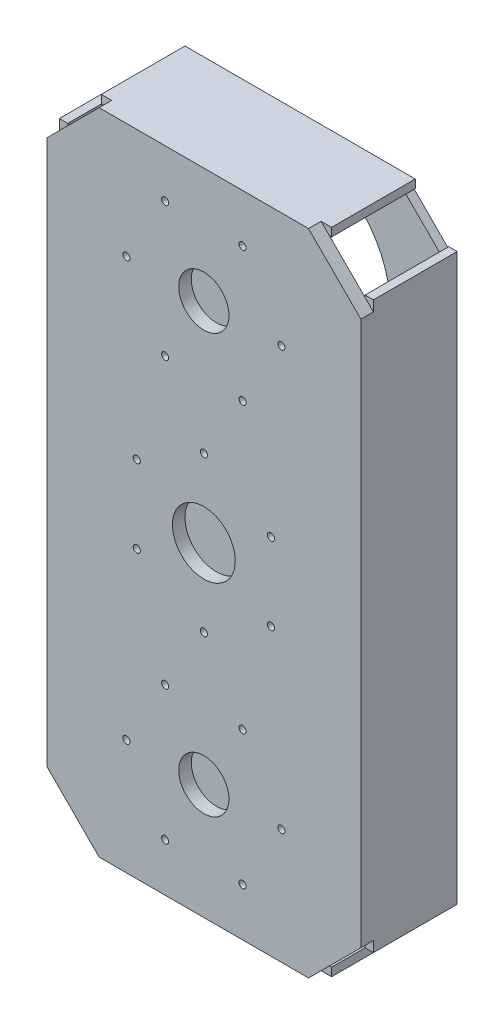
SolidWorks part; units mm, degrees
material "6061-T6 (SS)"
ref_plane "Front Plane" through (0, 0, 0) normal (0, 0, 1) x (1, 0, 0)
ref_plane "Top Plane" through (0, 0, 0) normal (0, 1, 0) x (1, 0, 0)
ref_plane "Right Plane" through (0, 0, 0) normal (1, 0, 0) x (0, 0, -1)
ref_plane "PL_Top_Plate_base" through (0, 0, 131) normal (0, 0, 1) x (1, 0, 0)
sketch "SK_Top_Plate" plane through (0, 0, 131) normal (0, 0, 1) x (1, 0, 0)
  line L0 (-50, -155) -> (50, -155)
  line L1 (50, -155) -> (75, -130)
  line L2 (75, -130) -> (75, 130)
  line L3 (75, 130) -> (50, 155)
  line L4 (50, 155) -> (-50, 155)
  line L5 (-50, 155) -> (-75, 130)
  line L6 (-75, 130) -> (-75, -130)
  line L7 (-75, -130) -> (-50, -155)
  circle A0 centre (37, 100) radius 1.7
  circle A1 centre (18.5, 132.0429) radius 1.7
  circle A2 centre (-18.5, 132.0429) radius 1.7
  circle A3 centre (-37, 100) radius 1.7
  circle A4 centre (-18.5, 67.9571) radius 1.7
  circle A5 centre (18.5, 67.9571) radius 1.7
  circle A6 centre (0, 100) radius 12
  circle A7 centre (37, -100) radius 1.7
  circle A8 centre (18.5, -67.9571) radius 1.7
  circle A9 centre (-18.5, -67.9571) radius 1.7
  circle A10 centre (-37, -100) radius 1.7
  circle A11 centre (-18.5, -132.0429) radius 1.7
  circle A12 centre (18.5, -132.0429) radius 1.7
  circle A13 centre (0, -100) radius 12
  circle A14 centre (32.0429, 18.5) radius 1.7
  circle A15 centre (0, 37) radius 1.7
  circle A16 centre (-32.0429, 18.5) radius 1.7
  circle A17 centre (-32.0429, -18.5) radius 1.7
  circle A18 centre (0, -37) radius 1.7
  circle A19 centre (32.0429, -18.5) radius 1.7
  circle A20 centre (0, 0) radius 15
  dimension "D17_SK_Top_Plate" = 3.4
  dimension "D20_SK_Top_Plate" = 3.4
  dimension "D23_SK_Top_Plate" = 3.4
  dimension "D26_SK_Top_Plate" = 3.4
  dimension "D29_SK_Top_Plate" = 3.4
  dimension "D32_SK_Top_Plate" = 3.4
  dimension "D35_SK_Top_Plate" = 24
  dimension "D37_SK_Top_Plate" = 3.4
  dimension "D40_SK_Top_Plate" = 3.4
  dimension "D43_SK_Top_Plate" = 3.4
  dimension "D46_SK_Top_Plate" = 3.4
  dimension "D49_SK_Top_Plate" = 3.4
  dimension "D52_SK_Top_Plate" = 3.4
  dimension "D55_SK_Top_Plate" = 24
  dimension "D57_SK_Top_Plate" = 3.4
  dimension "D60_SK_Top_Plate" = 3.4
  dimension "D62_SK_Top_Plate" = 3.4
  dimension "D65_SK_Top_Plate" = 3.4
  dimension "D68_SK_Top_Plate" = 3.4
  dimension "D70_SK_Top_Plate" = 3.4
  dimension "D73_SK_Top_Plate" = 30
  dimension "P1" = 50
  dimension "P2" = 155
  dimension "P3" = 50
  dimension "P4" = 155
  dimension "P5" = 75
  dimension "P6" = 130
  dimension "P7" = 75
  dimension "P8" = 130
  dimension "P9" = 50
  dimension "P10" = 155
  dimension "P11" = 50
  dimension "P12" = 155
  dimension "P13" = 75
  dimension "P14" = 130
  dimension "P15" = 75
  dimension "P16" = 130
  dimension "P18" = 37
  dimension "P19" = 100
  dimension "P21" = 18.5
  dimension "P22" = 132.0429
  dimension "P24" = 18.5
  dimension "P25" = 132.0429
  dimension "P27" = 37
  dimension "P28" = 100
  dimension "P30" = 18.5
  dimension "P31" = 67.9571
  dimension "P33" = 18.5
  dimension "P34" = 67.9571
  dimension "P36" = 100
  dimension "P38" = 37
  dimension "P39" = 100
  dimension "P41" = 18.5
  dimension "P42" = 67.9571
  dimension "P44" = 18.5
  dimension "P45" = 67.9571
  dimension "P47" = 37
  dimension "P48" = 100
  dimension "P50" = 18.5
  dimension "P51" = 132.0429
  dimension "P53" = 18.5
  dimension "P54" = 132.0429
  dimension "P56" = 100
  dimension "P58" = 32.0429
  dimension "P59" = 18.5
  dimension "P61" = 37
  dimension "P63" = 32.0429
  dimension "P64" = 18.5
  dimension "P66" = 32.0429
  dimension "P67" = 18.5
  dimension "P69" = 37
  dimension "P71" = 32.0429
  dimension "P72" = 18.5
extrude "Top_Plate" add sketch "SK_Top_Plate" along normal blind 6
ref_plane "PL_Front_Wall_base" through (71, 0, 0) normal (1, 0, 0) x (0, 0, -1)
sketch "SK_Front_Wall" plane through (71, 0, 0) normal (1, 0, 0) x (0, 0, -1)
  line L0 (-91, -135) -> (-91, 135)
  line L1 (-91, 135) -> (-131, 135)
  line L2 (-131, 135) -> (-131, -135)
  line L3 (-131, -135) -> (-91, -135)
  dimension "P1" = 91
  dimension "P2" = 135
  dimension "P3" = 91
  dimension "P4" = 135
  dimension "P5" = 131
  dimension "P6" = 135
  dimension "P7" = 131
  dimension "P8" = 135
extrude "Front_Wall" add sketch "SK_Front_Wall" along normal blind 4
ref_plane "PL_Back_Wall_base" through (-75, 0, 0) normal (1, 0, 0) x (0, 0, -1)
sketch "SK_Back_Wall" plane through (-75, 0, 0) normal (1, 0, 0) x (0, 0, -1)
  line L0 (-91, -135) -> (-91, 135)
  line L1 (-91, 135) -> (-131, 135)
  line L2 (-131, 135) -> (-131, -135)
  line L3 (-131, -135) -> (-91, -135)
  dimension "P1" = 91
  dimension "P2" = 135
  dimension "P3" = 91
  dimension "P4" = 135
  dimension "P5" = 131
  dimension "P6" = 135
  dimension "P7" = 131
  dimension "P8" = 135
extrude "Back_Wall" add sketch "SK_Back_Wall" along normal blind 4
ref_plane "PL_Left_Wall_base" through (0, 151, 0) normal (0, 1, 0) x (1, 0, 0)
sketch "SK_Left_Wall" plane through (0, 151, 0) normal (0, 1, 0) x (1, 0, 0)
  line L0 (-55, -91) -> (55, -91)
  line L1 (55, -91) -> (55, -131)
  line L2 (55, -131) -> (-55, -131)
  line L3 (-55, -131) -> (-55, -91)
  dimension "P1" = 55
  dimension "P2" = 91
  dimension "P3" = 55
  dimension "P4" = 91
  dimension "P5" = 55
  dimension "P6" = 131
  dimension "P7" = 55
  dimension "P8" = 131
extrude "Left_Wall" add sketch "SK_Left_Wall" along normal blind 4
ref_plane "PL_Right_Wall_base" through (0, -155, 0) normal (0, 1, 0) x (1, 0, 0)
sketch "SK_Right_Wall" plane through (0, -155, 0) normal (0, 1, 0) x (1, 0, 0)
  line L0 (-55, -91) -> (55, -91)
  line L1 (55, -91) -> (55, -131)
  line L2 (55, -131) -> (-55, -131)
  line L3 (-55, -131) -> (-55, -91)
  dimension "P1" = 55
  dimension "P2" = 91
  dimension "P3" = 55
  dimension "P4" = 91
  dimension "P5" = 55
  dimension "P6" = 131
  dimension "P7" = 55
  dimension "P8" = 131
extrude "Right_Wall" add sketch "SK_Right_Wall" along normal blind 4
ref_plane "PL_Bottom_Plate_base" through (0, 0, 91) normal (0, 0, 1) x (1, 0, 0)
sketch "SK_Bottom_Plate" plane through (0, 0, 91) normal (0, 0, 1) x (1, 0, 0)
  line L0 (-50, -155) -> (50, -155)
  line L1 (50, -155) -> (75, -130)
  line L2 (75, -130) -> (75, 130)
  line L3 (75, 130) -> (50, 155)
  line L4 (50, 155) -> (-50, 155)
  line L5 (-50, 155) -> (-75, 130)
  line L6 (-75, 130) -> (-75, -130)
  line L7 (-75, -130) -> (-50, -155)
  circle A0 centre (0, 100) radius 47
  circle A1 centre (0, -100) radius 47
  circle A2 centre (0, 0) radius 20
  dimension "D17_SK_Bottom_Plate" = 94
  dimension "D19_SK_Bottom_Plate" = 94
  dimension "D21_SK_Bottom_Plate" = 40
  dimension "P1" = 50
  dimension "P2" = 155
  dimension "P3" = 50
  dimension "P4" = 155
  dimension "P5" = 75
  dimension "P6" = 130
  dimension "P7" = 75
  dimension "P8" = 130
  dimension "P9" = 50
  dimension "P10" = 155
  dimension "P11" = 50
  dimension "P12" = 155
  dimension "P13" = 75
  dimension "P14" = 130
  dimension "P15" = 75
  dimension "P16" = 130
  dimension "P18" = 100
  dimension "P20" = 100
extrude "Bottom_Plate" add sketch "SK_Bottom_Plate" along normal blind 4
equation "\"Hip_spacing\"= 200"
equation "\"Pelvis_half_width\"= 155"
equation "\"Pelvis_half_depth\"= 75"
